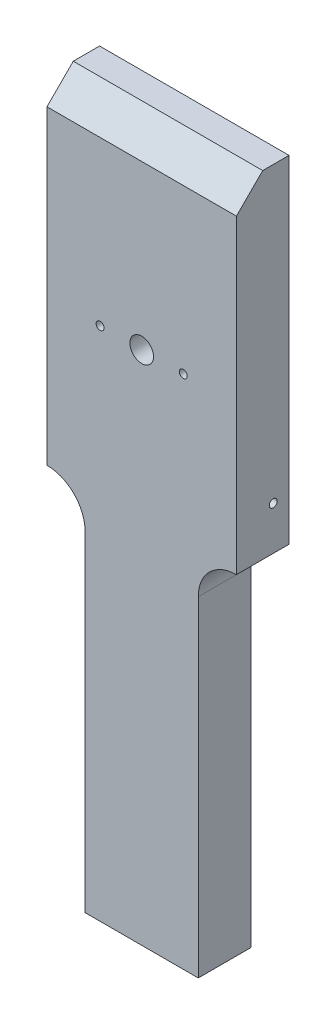
SolidWorks part; units mm, degrees
material "Pine"
ref_plane "Front Plane" through (0, 0, 0) normal (0, 0, 1) x (1, 0, 0)
ref_plane "Top Plane" through (0, 0, 0) normal (0, 1, 0) x (1, 0, 0)
ref_plane "Right Plane" through (0, 0, 0) normal (1, 0, 0) x (0, 0, -1)
sketch "Sketch1" plane through (0, 0, 0) normal (0, 0, 1) x (1, 0, 0)
  line L0 (0, 0) -> (0, -50000) construction
  line L1 (114.3, 203.2) -> (-114.3, 203.2)
  line L2 (114.3, 203.2) -> (114.3, -203.2)
  line L3 (114.3, -203.2) -> (-114.3, -203.2)
  line L4 (-114.3, 203.2) -> (-114.3, -203.2)
  line L5 (114.3, 203.2) -> (-114.3, -203.2) construction
  line L6 (114.3, -203.2) -> (-114.3, 203.2) construction
  line L7 (-68.2625, -647.7) -> (68.2625, -647.7)
  line L8 (-68.2625, -647.7) -> (-68.2625, -203.2)
  line L9 (-68.2625, -203.2) -> (68.2625, -203.2)
  line L10 (68.2625, -647.7) -> (68.2625, -203.2)
  line L11 (-68.2625, -647.7) -> (68.2625, -203.2) construction
  line L12 (-68.2625, -203.2) -> (68.2625, -647.7) construction
  line L14 (-50.1741, -25.4) -> (50.1741, -25.4) construction
  circle A3 centre (0, -25.4) radius 14.2875 construction
  circle A4 centre (0, -25.4) radius 14.2875
  circle A5 centre (-50.1741, -25.4) radius 4.7625
  circle A6 centre (50.1741, -25.4) radius 4.7625
  point P0 (0, 0)
  point P6 (0, -425.45)
  point P25 (0, -25.4)
  dimension "D8" = 9.525
  dimension "D1" = 136.525
  dimension "D2" = 444.5
  dimension "D3" = 406.4
  dimension "D4" = 228.6
extrude "Boss-Extrude1" add sketch "Sketch1" along normal blind 63.5 contours L7 L10 L3 L8 | L4 L3 L2 L1 | A4 | A5 | A6 region at (0, -425.45, 0)
sketch "Sketch2" plane through (0, 0, 0) normal (0, 0, -1) x (-1, 0, 0)
  line L0 (0, 0) -> (0, -50000) construction
  line L2 (-19.05, -128.5875) -> (19.05, -128.5875)
  line L3 (-19.05, -128.5875) -> (-19.05, -623.8875)
  line L4 (-19.05, -623.8875) -> (19.05, -623.8875)
  line L5 (19.05, -128.5875) -> (19.05, -623.8875)
  line L6 (-19.05, -128.5875) -> (19.05, -623.8875) construction
  line L7 (-19.05, -623.8875) -> (19.05, -128.5875) construction
  circle A2 centre (0, -25.4) radius 103.1875
  circle A3 centre (0, -25.4) radius 103.1875 construction
  point P3 (0, -376.2375)
  dimension "D1" = 38.1
  dimension "D2" = 495.3
  dimension "D3" = 88.9
extrude "Cut-Extrude1" cut sketch "Sketch2" against normal blind 36.5125
sketch "Sketch3" plane through (-114.3, 0, 0) normal (-1, 0, 0) x (0, 0, 1)
  line L0 (0, 203.2) -> (0, -203.2) construction
  line L6 (0, -128.5875) -> (0, -623.8875)
  line L7 (0, -623.8875) -> (36.5125, -623.8875)
  line L8 (36.5125, -623.8875) -> (36.5125, -128.5875)
  line L9 (36.5125, -128.5875) -> (0, -128.5875)
  line L10 (0, -128.5875) -> (0, -623.8875)
  line L11 (0, -623.8875) -> (36.5125, -623.8875)
  line L12 (36.5125, -623.8875) -> (36.5125, -128.5875)
  line L13 (36.5125, -128.5875) -> (0, -128.5875)
  circle A0 centre (19.05, -150.8125) radius 4.7625
  dimension "D4" = 9.525
  dimension "D1" = 19.05
  dimension "D2" = 0
  dimension "D3" = 22.225
extrude "Cut-Extrude2" cut sketch "Sketch3" against normal through all contours A0 region at (-114.3, -150.8125, 19.05)
fillet "Fillet1" radius 46.0375 2 edges at (68.2625, -203.2, 31.75) (-68.2625, -203.2, 31.75)
chamfer "Chamfer1" distance 31.75 angle 45 1 edges at (0, 203.2, 63.5)
